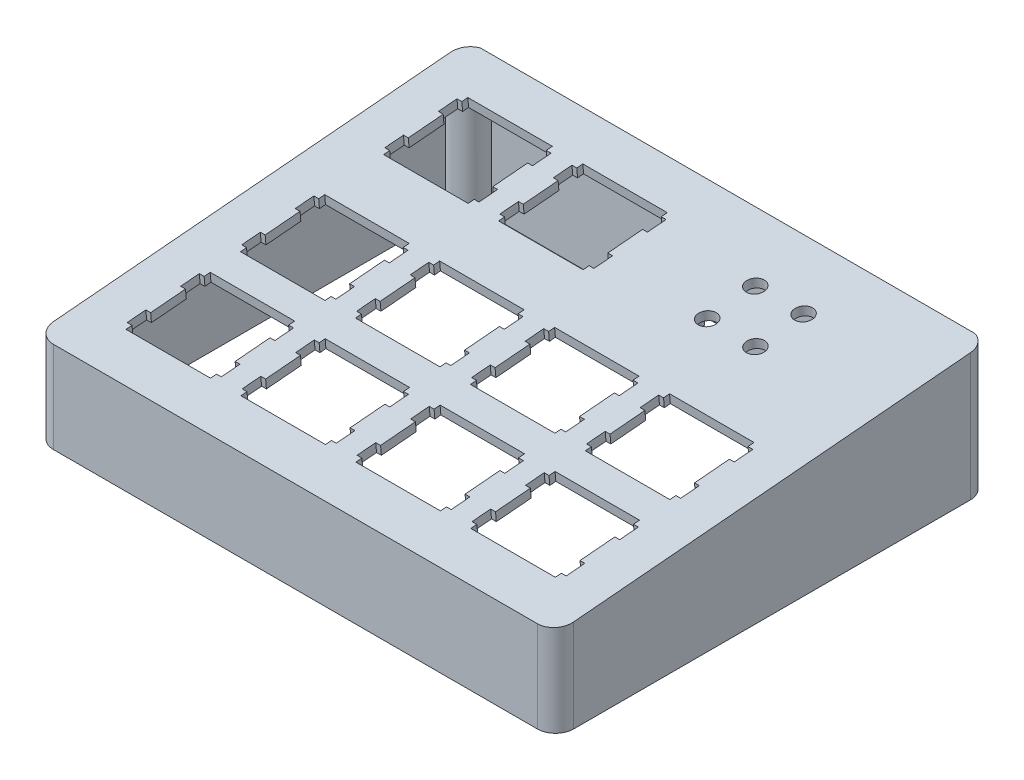
SolidWorks part; units mm, degrees
material "ABS"
ref_plane "Front" through (0, 0, 0) normal (0, 0, 1) x (1, 0, 0)
ref_plane "Top" through (0, 0, 0) normal (0, 1, 0) x (1, 0, 0)
ref_plane "Right" through (0, 0, 0) normal (1, 0, 0) x (0, 0, -1)
ref_axis "Axis1" through (80.9, 0, 0) along (-1, 0, 0)
ref_plane "Plane1" through (0, 0, 0) normal (0, 0.9962, 0.0872) x (1, 0, 0)
sketch "Sketch2" plane through (0, 0, 0) normal (0, 0.9962, 0.0872) x (1, 0, 0)
  line L1 (-43.1005, -35.9565) -> (43.1005, -35.9565)
  line L2 (-43.1005, -35.9565) -> (-43.1005, 35.9565)
  line L3 (-43.1005, 35.9565) -> (43.1005, 35.9565)
  line L4 (43.1005, -35.9565) -> (43.1005, 35.9565)
  line L5 (-43.1005, -35.9565) -> (43.1005, 35.9565) construction
  line L6 (-43.1005, 35.9565) -> (43.1005, -35.9565) construction
  point P0 (0, 0)
  dimension "D1" = 71.913
  dimension "D2" = 86.201
extrude "Boss-Extrude1" add sketch "Sketch2" along normal mid plane 1.5
sketch "Sketch7" plane through (0, 0.7471, 0.0654) normal (0, 0.9962, 0.0872) x (1, 0, 0)
  line L0 (16.5245, -2.3805) -> (21.5745, -2.3805) construction
  line L1 (19.0495, -2.3805) -> (19.0495, 21.432) construction
  line L2 (15.0495, 25.432) -> (23.0495, 25.432) construction
  line L3 (15.0495, 25.432) -> (15.0495, 17.432) construction
  line L4 (15.0495, 17.432) -> (23.0495, 17.432) construction
  line L5 (23.0495, 25.432) -> (23.0495, 17.432) construction
  line L6 (15.0495, 25.432) -> (23.0495, 17.432) construction
  line L7 (15.0495, 17.432) -> (23.0495, 25.432) construction
  line L8 (-43.1005, 35.9565) -> (-43.1005, -35.9565) construction
  line L9 (-43.1005, -35.9565) -> (43.1005, -35.9565) construction
  circle A0 centre (15.0495, 25.432) radius 1.5
  circle A1 centre (23.0495, 25.432) radius 1.5
  circle A2 centre (23.0495, 17.432) radius 1.5
  circle A3 centre (15.0495, 17.432) radius 1.5
  point P5 (-2.5255, 21.432)
  line B0 (43.1005, -35.9565) -> (-43.1005, -35.9565)
  line B1 (-43.1005, -35.9565) -> (-43.1005, 35.9565)
  line B2 (-43.1005, 35.9565) -> (43.1005, 35.9565)
  line B3 (43.1005, 35.9565) -> (43.1005, -35.9565)
  line B4 (21.5745, -14.4305) -> (21.5745, -15.4305)
  line B5 (21.5745, -15.4305) -> (20.7745, -15.4305)
  line B6 (20.7745, -15.4305) -> (20.7745, -18.5305)
  line B7 (20.7745, -18.5305) -> (21.5745, -18.5305)
  line B8 (21.5745, -18.5305) -> (21.5745, -24.3305)
  line B9 (21.5745, -24.3305) -> (20.7745, -24.3305)
  line B10 (20.7745, -24.3305) -> (20.7745, -27.4305)
  line B11 (20.7745, -27.4305) -> (21.5745, -27.4305)
  line B12 (21.5745, -27.4305) -> (21.5745, -28.4305)
  line B13 (21.5745, -28.4305) -> (35.5745, -28.4305)
  line B14 (35.5745, -28.4305) -> (35.5745, -27.4305)
  line B15 (35.5745, -27.4305) -> (36.3745, -27.4305)
  line B16 (36.3745, -27.4305) -> (36.3745, -24.3305)
  line B17 (36.3745, -24.3305) -> (35.5745, -24.3305)
  line B18 (35.5745, -24.3305) -> (35.5745, -18.5305)
  line B19 (35.5745, -18.5305) -> (36.3745, -18.5305)
  line B20 (36.3745, -18.5305) -> (36.3745, -15.4305)
  line B21 (36.3745, -15.4305) -> (35.5745, -15.4305)
  line B22 (35.5745, -15.4305) -> (35.5745, -14.4305)
  line B23 (35.5745, -14.4305) -> (21.5745, -14.4305)
  line B24 (2.5245, -14.4305) -> (2.5245, -15.4305)
  line B25 (2.5245, -15.4305) -> (1.7245, -15.4305)
  line B26 (1.7245, -15.4305) -> (1.7245, -18.5305)
  line B27 (1.7245, -18.5305) -> (2.5245, -18.5305)
  line B28 (2.5245, -18.5305) -> (2.5245, -24.3305)
  line B29 (2.5245, -24.3305) -> (1.7245, -24.3305)
  line B30 (1.7245, -24.3305) -> (1.7245, -27.4305)
  line B31 (1.7245, -27.4305) -> (2.5245, -27.4305)
  line B32 (2.5245, -27.4305) -> (2.5245, -28.4305)
  line B33 (2.5245, -28.4305) -> (16.5245, -28.4305)
  line B34 (16.5245, -28.4305) -> (16.5245, -27.4305)
  line B35 (16.5245, -27.4305) -> (17.3245, -27.4305)
  line B36 (17.3245, -27.4305) -> (17.3245, -24.3305)
  line B37 (17.3245, -24.3305) -> (16.5245, -24.3305)
  line B38 (16.5245, -24.3305) -> (16.5245, -18.5305)
  line B39 (16.5245, -18.5305) -> (17.3245, -18.5305)
  line B40 (17.3245, -18.5305) -> (17.3245, -15.4305)
  line B41 (17.3245, -15.4305) -> (16.5245, -15.4305)
  line B42 (16.5245, -15.4305) -> (16.5245, -14.4305)
  line B43 (16.5245, -14.4305) -> (2.5245, -14.4305)
  line B44 (-16.5255, -14.4305) -> (-16.5255, -15.4305)
  line B45 (-16.5255, -15.4305) -> (-17.3255, -15.4305)
  line B46 (-17.3255, -15.4305) -> (-17.3255, -18.5305)
  line B47 (-17.3255, -18.5305) -> (-16.5255, -18.5305)
  line B48 (-16.5255, -18.5305) -> (-16.5255, -24.3305)
  line B49 (-16.5255, -24.3305) -> (-17.3255, -24.3305)
  line B50 (-17.3255, -24.3305) -> (-17.3255, -27.4305)
  line B51 (-17.3255, -27.4305) -> (-16.5255, -27.4305)
  line B52 (-16.5255, -27.4305) -> (-16.5255, -28.4305)
  line B53 (-16.5255, -28.4305) -> (-2.5255, -28.4305)
  line B54 (-2.5255, -28.4305) -> (-2.5255, -27.4305)
  line B55 (-2.5255, -27.4305) -> (-1.7255, -27.4305)
  line B56 (-1.7255, -27.4305) -> (-1.7255, -24.3305)
  line B57 (-1.7255, -24.3305) -> (-2.5255, -24.3305)
  line B58 (-2.5255, -24.3305) -> (-2.5255, -18.5305)
  line B59 (-2.5255, -18.5305) -> (-1.7255, -18.5305)
  line B60 (-1.7255, -18.5305) -> (-1.7255, -15.4305)
  line B61 (-1.7255, -15.4305) -> (-2.5255, -15.4305)
  line B62 (-2.5255, -15.4305) -> (-2.5255, -14.4305)
  line B63 (-2.5255, -14.4305) -> (-16.5255, -14.4305)
  line B64 (-35.5765, -14.4305) -> (-35.5765, -15.4305)
  line B65 (-35.5765, -15.4305) -> (-36.3765, -15.4305)
  line B66 (-36.3765, -15.4305) -> (-36.3765, -18.5305)
  line B67 (-36.3765, -18.5305) -> (-35.5765, -18.5305)
  line B68 (-35.5765, -18.5305) -> (-35.5765, -24.3305)
  line B69 (-35.5765, -24.3305) -> (-36.3765, -24.3305)
  line B70 (-36.3765, -24.3305) -> (-36.3765, -27.4305)
  line B71 (-36.3765, -27.4305) -> (-35.5765, -27.4305)
  line B72 (-35.5765, -27.4305) -> (-35.5765, -28.4305)
  line B73 (-35.5765, -28.4305) -> (-21.5755, -28.4305)
  line B74 (-21.5755, -28.4305) -> (-21.5755, -27.4305)
  line B75 (-21.5755, -27.4305) -> (-20.7755, -27.4305)
  line B76 (-20.7755, -27.4305) -> (-20.7755, -24.3305)
  line B77 (-20.7755, -24.3305) -> (-21.5755, -24.3305)
  line B78 (-21.5755, -24.3305) -> (-21.5755, -18.5305)
  line B79 (-21.5755, -18.5305) -> (-20.7755, -18.5305)
  line B80 (-20.7755, -18.5305) -> (-20.7755, -15.4305)
  line B81 (-20.7755, -15.4305) -> (-21.5755, -15.4305)
  line B82 (-21.5755, -15.4305) -> (-21.5755, -14.4305)
  line B83 (-21.5755, -14.4305) -> (-35.5765, -14.4305)
  line B84 (21.5745, 4.6195) -> (21.5745, 3.6195)
  line B85 (21.5745, 3.6195) -> (20.7745, 3.6195)
  line B86 (20.7745, 3.6195) -> (20.7745, 0.5195)
  line B87 (20.7745, 0.5195) -> (21.5745, 0.5195)
  line B88 (21.5745, 0.5195) -> (21.5745, -5.2805)
  line B89 (21.5745, -5.2805) -> (20.7745, -5.2805)
  line B90 (20.7745, -5.2805) -> (20.7745, -8.3805)
  line B91 (20.7745, -8.3805) -> (21.5745, -8.3805)
  line B92 (21.5745, -8.3805) -> (21.5745, -9.3805)
  line B93 (21.5745, -9.3805) -> (35.5745, -9.3805)
  line B94 (35.5745, -9.3805) -> (35.5745, -8.3805)
  line B95 (35.5745, -8.3805) -> (36.3745, -8.3805)
  line B96 (36.3745, -8.3805) -> (36.3745, -5.2805)
  line B97 (36.3745, -5.2805) -> (35.5745, -5.2805)
  line B98 (35.5745, -5.2805) -> (35.5745, 0.5195)
  line B99 (35.5745, 0.5195) -> (36.3745, 0.5195)
  line B100 (36.3745, 0.5195) -> (36.3745, 3.6195)
  line B101 (36.3745, 3.6195) -> (35.5745, 3.6195)
  line B102 (35.5745, 3.6195) -> (35.5745, 4.6195)
  line B103 (35.5745, 4.6195) -> (21.5745, 4.6195)
  line B104 (2.5245, 4.6195) -> (2.5245, 3.6195)
  line B105 (2.5245, 3.6195) -> (1.7245, 3.6195)
  line B106 (1.7245, 3.6195) -> (1.7245, 0.5195)
  line B107 (1.7245, 0.5195) -> (2.5245, 0.5195)
  line B108 (2.5245, 0.5195) -> (2.5245, -5.2805)
  line B109 (2.5245, -5.2805) -> (1.7245, -5.2805)
  line B110 (1.7245, -5.2805) -> (1.7245, -8.3805)
  line B111 (1.7245, -8.3805) -> (2.5245, -8.3805)
  line B112 (2.5245, -8.3805) -> (2.5245, -9.3805)
  line B113 (2.5245, -9.3805) -> (16.5245, -9.3805)
  line B114 (16.5245, -9.3805) -> (16.5245, -8.3805)
  line B115 (16.5245, -8.3805) -> (17.3245, -8.3805)
  line B116 (17.3245, -8.3805) -> (17.3245, -5.2805)
  line B117 (17.3245, -5.2805) -> (16.5245, -5.2805)
  line B118 (16.5245, -5.2805) -> (16.5245, 0.5195)
  line B119 (16.5245, 0.5195) -> (17.3245, 0.5195)
  line B120 (17.3245, 0.5195) -> (17.3245, 3.6195)
  line B121 (17.3245, 3.6195) -> (16.5245, 3.6195)
  line B122 (16.5245, 3.6195) -> (16.5245, 4.6195)
  line B123 (16.5245, 4.6195) -> (2.5245, 4.6195)
  line B124 (-16.5255, 4.6195) -> (-16.5255, 3.6195)
  line B125 (-16.5255, 3.6195) -> (-17.3255, 3.6195)
  line B126 (-17.3255, 3.6195) -> (-17.3255, 0.5195)
  line B127 (-17.3255, 0.5195) -> (-16.5255, 0.5195)
  line B128 (-16.5255, 0.5195) -> (-16.5255, -5.2805)
  line B129 (-16.5255, -5.2805) -> (-17.3255, -5.2805)
  line B130 (-17.3255, -5.2805) -> (-17.3255, -8.3805)
  line B131 (-17.3255, -8.3805) -> (-16.5255, -8.3805)
  line B132 (-16.5255, -8.3805) -> (-16.5255, -9.3805)
  line B133 (-16.5255, -9.3805) -> (-2.5255, -9.3805)
  line B134 (-2.5255, -9.3805) -> (-2.5255, -8.3805)
  line B135 (-2.5255, -8.3805) -> (-1.7255, -8.3805)
  line B136 (-1.7255, -8.3805) -> (-1.7255, -5.2805)
  line B137 (-1.7255, -5.2805) -> (-2.5255, -5.2805)
  line B138 (-2.5255, -5.2805) -> (-2.5255, 0.5195)
  line B139 (-2.5255, 0.5195) -> (-1.7255, 0.5195)
  line B140 (-1.7255, 0.5195) -> (-1.7255, 3.6195)
  line B141 (-1.7255, 3.6195) -> (-2.5255, 3.6195)
  line B142 (-2.5255, 3.6195) -> (-2.5255, 4.6195)
  line B143 (-2.5255, 4.6195) -> (-16.5255, 4.6195)
  line B144 (-35.5765, 4.6195) -> (-35.5765, 3.6195)
  line B145 (-35.5765, 3.6195) -> (-36.3765, 3.6195)
  line B146 (-36.3765, 3.6195) -> (-36.3765, 0.5195)
  line B147 (-36.3765, 0.5195) -> (-35.5765, 0.5195)
  line B148 (-35.5765, 0.5195) -> (-35.5765, -5.2805)
  line B149 (-35.5765, -5.2805) -> (-36.3765, -5.2805)
  line B150 (-36.3765, -5.2805) -> (-36.3765, -8.3805)
  line B151 (-36.3765, -8.3805) -> (-35.5765, -8.3805)
  line B152 (-35.5765, -8.3805) -> (-35.5765, -9.3805)
  line B153 (-35.5765, -9.3805) -> (-21.5755, -9.3805)
  line B154 (-21.5755, -9.3805) -> (-21.5755, -8.3805)
  line B155 (-21.5755, -8.3805) -> (-20.7755, -8.3805)
  line B156 (-20.7755, -8.3805) -> (-20.7755, -5.2805)
  line B157 (-20.7755, -5.2805) -> (-21.5755, -5.2805)
  line B158 (-21.5755, -5.2805) -> (-21.5755, 0.5195)
  line B159 (-21.5755, 0.5195) -> (-20.7755, 0.5195)
  line B160 (-20.7755, 0.5195) -> (-20.7755, 3.6195)
  line B161 (-20.7755, 3.6195) -> (-21.5755, 3.6195)
  line B162 (-21.5755, 3.6195) -> (-21.5755, 4.6195)
  line B163 (-21.5755, 4.6195) -> (-35.5765, 4.6195)
  line B164 (-16.5255, 28.4325) -> (-16.5255, 27.4325)
  line B165 (-16.5255, 27.4325) -> (-17.3255, 27.4325)
  line B166 (-17.3255, 27.4325) -> (-17.3255, 24.3315)
  line B167 (-17.3255, 24.3315) -> (-16.5255, 24.3315)
  line B168 (-16.5255, 24.3315) -> (-16.5255, 18.5325)
  line B169 (-16.5255, 18.5325) -> (-17.3255, 18.5325)
  line B170 (-17.3255, 18.5325) -> (-17.3255, 15.4315)
  line B171 (-17.3255, 15.4315) -> (-16.5255, 15.4315)
  line B172 (-16.5255, 15.4315) -> (-16.5255, 14.4315)
  line B173 (-16.5255, 14.4315) -> (-2.5255, 14.4315)
  line B174 (-2.5255, 14.4315) -> (-2.5255, 15.4315)
  line B175 (-2.5255, 15.4315) -> (-1.7255, 15.4315)
  line B176 (-1.7255, 15.4315) -> (-1.7255, 18.5325)
  line B177 (-1.7255, 18.5325) -> (-2.5255, 18.5325)
  line B178 (-2.5255, 18.5325) -> (-2.5255, 24.3315)
  line B179 (-2.5255, 24.3315) -> (-1.7255, 24.3315)
  line B180 (-1.7255, 24.3315) -> (-1.7255, 27.4325)
  line B181 (-1.7255, 27.4325) -> (-2.5255, 27.4325)
  line B182 (-2.5255, 27.4325) -> (-2.5255, 28.4325)
  line B183 (-2.5255, 28.4325) -> (-16.5255, 28.4325)
  line B184 (-35.5765, 28.4325) -> (-35.5765, 27.4325)
  line B185 (-35.5765, 27.4325) -> (-36.3765, 27.4325)
  line B186 (-36.3765, 27.4325) -> (-36.3765, 24.3315)
  line B187 (-36.3765, 24.3315) -> (-35.5765, 24.3315)
  line B188 (-35.5765, 24.3315) -> (-35.5765, 18.5325)
  line B189 (-35.5765, 18.5325) -> (-36.3765, 18.5325)
  line B190 (-36.3765, 18.5325) -> (-36.3765, 15.4315)
  line B191 (-36.3765, 15.4315) -> (-35.5765, 15.4315)
  line B192 (-35.5765, 15.4315) -> (-35.5765, 14.4315)
  line B193 (-35.5765, 14.4315) -> (-21.5755, 14.4315)
  line B194 (-21.5755, 14.4315) -> (-21.5755, 15.4315)
  line B195 (-21.5755, 15.4315) -> (-20.7755, 15.4315)
  line B196 (-20.7755, 15.4315) -> (-20.7755, 18.5325)
  line B197 (-20.7755, 18.5325) -> (-21.5755, 18.5325)
  line B198 (-21.5755, 18.5325) -> (-21.5755, 24.3315)
  line B199 (-21.5755, 24.3315) -> (-20.7755, 24.3315)
  line B200 (-20.7755, 24.3315) -> (-20.7755, 27.4325)
  line B201 (-20.7755, 27.4325) -> (-21.5755, 27.4325)
  line B202 (-21.5755, 27.4325) -> (-21.5755, 28.4325)
  line B203 (-21.5755, 28.4325) -> (-35.5765, 28.4325)
  dimension "D1" = 3
  dimension "D2" = 8
sketch_block_instance "Block1-1"
sketch_block "Block1"
extrude "Cut-Extrude1" cut sketch "Sketch7" against normal up to next contours B42 B43 B24 B25 B26 B27 B28 B29 B30 B31 B32 B33 B34 B35 B36 B37 B38 B39 B40 B41 | B22 B23 B4 B5 B6 B7 B8 B9 B10 B11 B12 B13 B14 B15 B16 B17 B18 B19 B20 B21 | B122 B123 B104 B105 B106 B107 B108 B109 B110 B111 B112 B113 B114 B115 B116 B117 B118 B119 B120 B121 | B62 B63 B44 B45 B46 B47 B48 B49 B50 B51 B52 B53 B54 B55 B56 B57 B58 B59 B60 B61 | B142 B143 B124 B125 B126 B127 B128 B129 B130 B131 B132 B133 B134 B135 B136 B137 B138 B139 B140 B141 | B82 B83 B64 B65 B66 B67 B68 B69 B70 B71 B72 B73 B74 B75 B76 B77 B78 B79 B80 B81 | B162 B163 B144 B145 B146 B147 B148 B149 B150 B151 B152 B153 B154 B155 B156 B157 B158 B159 B160 B161 | B102 B103 B84 B85 B86 B87 B88 B89 B90 B91 B92 B93 B94 B95 B96 B97 B98 B99 B100 B101 | B202 B203 B184 B185 B186 B187 B188 B189 B190 B191 B192 B193 B194 B195 B196 B197 B198 B199 B200 B201 | B182 B183 B164 B165 B166 B167 B168 B169 B170 B171 B172 B173 B174 B175 B176 B177 B178 B179 B180 B181 | A3 | A0 | A1 | A2 region at (15.0495, 2.9637, -25.2699) region at (23.0495, 2.9637, -25.2699) region at (23.0495, 2.2664, -17.3003) region at (15.0495, 2.2664, -17.3003) region at (28.5745, -1.1206, 21.4143) region at (9.5245, -1.1206, 21.4143) region at (-9.5255, -1.1206, 21.4143) region at (-28.576, -1.1206, 21.4143) region at (28.5745, 0.5397, 2.4368) region at (9.5245, 0.5397, 2.4368) region at (-9.5255, 0.5397, 2.4368) region at (-28.576, 0.5397, 2.4368) region at (-9.5255, 2.6151, -21.2851) region at (-28.576, 2.6151, -21.2851)
ref_plane "Plane2" through (0, -17.5, 0) normal (0, -1, 0) x (-1, 0, 0)
sketch "Sketch3" plane through (0, -17.5, 0) normal (0, -1, 0) x (-1, 0, 0)
  line L5 (-43.1005, 35.885) -> (43.1005, 35.885)
  line L6 (-43.1005, 35.885) -> (-43.1005, -35.885)
  line L7 (-43.1005, -35.885) -> (43.1005, -35.885)
  line L8 (43.1005, 35.885) -> (43.1005, -35.885)
extrude "Extrude-Thin1" add sketch "Sketch3" against normal up to next thin thin type one direction reverse wall 2
fillet "Fillet1" radius 3 4 edges at (43.1005, -7.5567, -35.885) (-43.1005, -7.5567, -35.885) (43.1005, -9.9433, 35.885) (-43.1005, -9.9433, 35.885)
sketch "Sketch4" plane through (0, -17.5, 0) normal (0, -1, 0) x (1, 0, 0)
  circle A1 centre (-40.1005, 32.885) radius 3
  arc A2 (-40.1005, 35.885) -> (-43.1005, 32.885) centre (-40.1005, 32.885) ccw construction
  circle A3 centre (40.1005, 32.885) radius 3
  circle A4 centre (40.1005, -32.885) radius 3
  circle A5 centre (-40.1005, -32.885) radius 3
  arc A6 (43.1005, 32.885) -> (40.1005, 35.885) centre (40.1005, 32.885) ccw construction
extrude "Boss-Extrude2" add sketch "Sketch4" against normal up to next
hole_wizard "Tap Drill for #2-56 Tap1" positions "Sketch5" profile "Sketch6" hole size "#2-56" standard "ANSI Inch"
sketch "Sketch5" plane through (0, -17.5, 0) normal (0, -1, 0) x (-1, 0, 0)
  point P0 (40.1005, -32.885)
  point P3 (-40.1005, -32.885)
  point P6 (-40.1005, 32.885)
  point P9 (40.1005, 32.885)
sketch "Sketch6" plane through (-40.1005, -17.5, 32.885) normal (1, 0, 0) x (0, 0, -1)
  line L0 (0, 0) -> (0, 13.2342)
  line L1 (0, 13.2342) -> (0.889, 12.7)
  line L2 (0.889, 12.7) -> (0.889, 0)
  line L5 (0.889, 0) -> (0, 0)
  line L10 (0, 13.2342) -> (-0.889, 12.7) construction
  line L11 (0, -6.35) -> (0, 107.95) construction
  dimension "Hole Dia." = 1.778
  dimension "Hole Depth" = 12.7
  dimension "Drill Angle" = 118
sketch "Sketch8" plane through (0, 0, -35.885) normal (0, 0, -1) x (-1, 0, 0)
  line L0 (40.1005, -17.5) -> (-40.1005, -17.5) construction
  line L1 (-4, -20.75) -> (4, -20.75)
  line L2 (-4, -20.75) -> (-4, -14.25)
  line L3 (-4, -14.25) -> (4, -14.25)
  line L4 (4, -20.75) -> (4, -14.25)
  line L5 (-4, -20.75) -> (4, -14.25) construction
  line L6 (-4, -14.25) -> (4, -20.75) construction
  point P0 (0, -17.5)
  dimension "D1" = 8
  dimension "D2" = 6.5
extrude "Cut-Extrude2" cut sketch "Sketch8" against normal up to next
